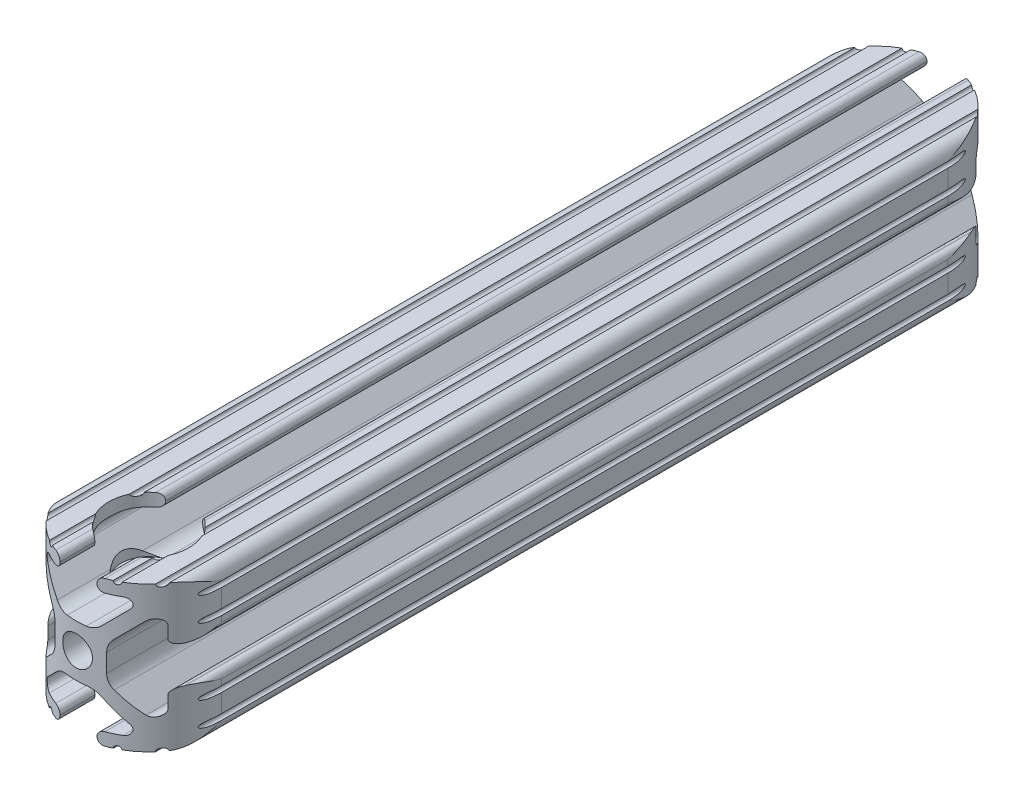
SolidWorks part; units mm, degrees
material "6061 Alloy"
ref_plane "Front Plane" through (0, 0, 0) normal (0, 0, 1) x (1, 0, 0)
ref_plane "Top Plane" through (0, 0, 0) normal (0, 1, 0) x (1, 0, 0)
ref_plane "Right Plane" through (0, 0, 0) normal (1, 0, 0) x (0, 0, -1)
sketch "Sketch1" plane through (0, 0, 0) normal (0, 0, 1) x (1, 0, 0)
  line L88 (-7.1797, -8.6452) -> (-3.9523, -5.4237)
  line L89 (-1.7093, -4.4958) -> (1.7093, -4.4958)
  line L90 (3.9523, -5.4237) -> (7.1797, -8.6452)
  line L91 (6.4164, -10.4902) -> (4.2875, -10.4902)
  line L92 (3.2385, -11.5392) -> (3.2385, -11.651)
  line L93 (4.2875, -12.7) -> (5.3171, -12.7)
  line L94 (6.3331, -12.7) -> (9.5504, -12.7)
  line L95 (12.7, -9.5504) -> (12.7, -6.3331)
  line L96 (12.7, -5.3171) -> (12.7, -4.2875)
  line L97 (11.651, -3.2385) -> (11.5392, -3.2385)
  line L98 (10.4902, -4.2875) -> (10.4902, -6.4021)
  line L99 (8.7371, -7.1294) -> (5.441, -3.8408)
  line L100 (4.5085, -1.5932) -> (4.5085, 1.5932)
  line L101 (5.441, 3.8408) -> (8.7371, 7.1294)
  line L102 (10.4902, 6.4021) -> (10.4902, 4.2875)
  line L103 (11.5392, 3.2385) -> (11.651, 3.2385)
  line L104 (12.7, 4.2875) -> (12.7, 5.3171)
  line L105 (12.7, 6.3331) -> (12.7, 9.5504)
  line L106 (9.5504, 12.7) -> (6.3331, 12.7)
  line L107 (5.3171, 12.7) -> (4.2875, 12.7)
  line L108 (3.2385, 11.651) -> (3.2385, 11.5392)
  line L109 (4.2875, 10.4902) -> (6.4768, 10.4902)
  line L110 (7.207, 8.7244) -> (3.8983, 5.4232)
  line L111 (1.6558, 4.4958) -> (-1.6558, 4.4958)
  line L112 (-3.8983, 5.4232) -> (-7.207, 8.7244)
  line L113 (-6.4768, 10.4902) -> (-4.2875, 10.4902)
  line L114 (-3.2385, 11.5392) -> (-3.2385, 11.651)
  line L115 (-4.2875, 12.7) -> (-5.3171, 12.7)
  line L116 (-6.3331, 12.7) -> (-9.5504, 12.7)
  line L117 (-12.7, 9.5504) -> (-12.7, 6.3331)
  line L118 (-12.7, 5.3171) -> (-12.7, 4.2875)
  line L119 (-11.651, 3.2385) -> (-11.5392, 3.2385)
  line L120 (-10.4902, 4.2875) -> (-10.4902, 6.4021)
  line L121 (-8.7371, 7.1294) -> (-5.441, 3.8408)
  line L122 (-4.5085, 1.5932) -> (-4.5085, -1.5932)
  line L123 (-5.441, -3.8408) -> (-8.7371, -7.1294)
  line L124 (-10.4902, -6.4021) -> (-10.4902, -4.2875)
  line L125 (-11.5392, -3.2385) -> (-11.651, -3.2385)
  line L126 (-12.7, -4.2875) -> (-12.7, -5.3171)
  line L127 (-12.7, -6.3331) -> (-12.7, -9.5504)
  line L128 (-9.5504, -12.7) -> (-6.3331, -12.7)
  line L129 (-5.3171, -12.7) -> (-4.2875, -12.7)
  line L130 (-3.2385, -11.651) -> (-3.2385, -11.5392)
  line L131 (-4.2875, -10.4902) -> (-6.4164, -10.4902)
  circle A1 centre (0, 0) radius 2.6035
  arc A104 (-7.1797, -8.6452) -> (-6.4164, -10.4902) centre (-6.4164, -9.4098) ccw
  arc A105 (-1.7093, -4.4958) -> (-3.9523, -5.4237) centre (-1.7093, -7.6708) ccw
  arc A106 (3.9523, -5.4237) -> (1.7093, -4.4958) centre (1.7093, -7.6708) ccw
  arc A107 (6.4164, -10.4902) -> (7.1797, -8.6452) centre (6.4164, -9.4098) ccw
  arc A108 (4.2875, -10.4902) -> (3.2385, -11.5392) centre (4.2875, -11.5392) ccw
  arc A109 (3.2385, -11.651) -> (4.2875, -12.7) centre (4.2875, -11.651) ccw
  arc A110 (6.3331, -12.7) -> (5.3171, -12.7) centre (5.8251, -12.7) ccw
  arc A111 (10.5664, -12.6998) -> (9.5504, -12.7) centre (10.0584, -12.7) ccw
  arc A112 (10.5664, -12.6998) -> (12.6998, -10.5664) centre (10.5918, -10.5918) ccw
  arc A113 (12.7, -9.5504) -> (12.6998, -10.5664) centre (12.7, -10.0584) ccw
  arc A114 (12.7, -5.3171) -> (12.7, -6.3331) centre (12.7, -5.8251) ccw
  arc A115 (12.7, -4.2875) -> (11.651, -3.2385) centre (11.651, -4.2875) ccw
  arc A116 (11.5392, -3.2385) -> (10.4902, -4.2875) centre (11.5392, -4.2875) ccw
  arc A117 (8.7371, -7.1294) -> (10.4902, -6.4021) centre (9.4628, -6.4021) ccw
  arc A118 (4.5085, -1.5932) -> (5.441, -3.8408) centre (7.6835, -1.5932) ccw
  arc A119 (5.441, 3.8408) -> (4.5085, 1.5932) centre (7.6835, 1.5932) ccw
  arc A120 (10.4902, 6.4021) -> (8.7371, 7.1294) centre (9.4628, 6.4021) ccw
  arc A121 (10.4902, 4.2875) -> (11.5392, 3.2385) centre (11.5392, 4.2875) ccw
  arc A122 (11.651, 3.2385) -> (12.7, 4.2875) centre (11.651, 4.2875) ccw
  arc A123 (12.7, 6.3331) -> (12.7, 5.3171) centre (12.7, 5.8251) ccw
  arc A124 (12.6998, 10.5664) -> (12.7, 9.5504) centre (12.7, 10.0584) ccw
  arc A125 (12.6998, 10.5664) -> (10.5664, 12.6998) centre (10.5918, 10.5918) ccw
  arc A126 (9.5504, 12.7) -> (10.5664, 12.6998) centre (10.0584, 12.7) ccw
  arc A127 (5.3171, 12.7) -> (6.3331, 12.7) centre (5.8251, 12.7) ccw
  arc A128 (4.2875, 12.7) -> (3.2385, 11.651) centre (4.2875, 11.651) ccw
  arc A129 (3.2385, 11.5392) -> (4.2875, 10.4902) centre (4.2875, 11.5392) ccw
  arc A130 (7.207, 8.7244) -> (6.4768, 10.4902) centre (6.4768, 9.4563) ccw
  arc A131 (1.6558, 4.4958) -> (3.8983, 5.4232) centre (1.6558, 7.6708) ccw
  arc A132 (-3.8983, 5.4232) -> (-1.6558, 4.4958) centre (-1.6558, 7.6708) ccw
  arc A133 (-6.4768, 10.4902) -> (-7.207, 8.7244) centre (-6.4768, 9.4563) ccw
  arc A134 (-4.2875, 10.4902) -> (-3.2385, 11.5392) centre (-4.2875, 11.5392) ccw
  arc A135 (-3.2385, 11.651) -> (-4.2875, 12.7) centre (-4.2875, 11.651) ccw
  arc A136 (-6.3331, 12.7) -> (-5.3171, 12.7) centre (-5.8251, 12.7) ccw
  arc A137 (-10.5664, 12.6998) -> (-9.5504, 12.7) centre (-10.0584, 12.7) ccw
  arc A138 (-10.5664, 12.6998) -> (-12.6998, 10.5664) centre (-10.5918, 10.5918) ccw
  arc A139 (-12.7, 9.5504) -> (-12.6998, 10.5664) centre (-12.7, 10.0584) ccw
  arc A140 (-12.7, 5.3171) -> (-12.7, 6.3331) centre (-12.7, 5.8251) ccw
  arc A141 (-12.7, 4.2875) -> (-11.651, 3.2385) centre (-11.651, 4.2875) ccw
  arc A142 (-11.5392, 3.2385) -> (-10.4902, 4.2875) centre (-11.5392, 4.2875) ccw
  arc A143 (-8.7371, 7.1294) -> (-10.4902, 6.4021) centre (-9.4628, 6.4021) ccw
  arc A144 (-4.5085, 1.5932) -> (-5.441, 3.8408) centre (-7.6835, 1.5932) ccw
  arc A145 (-5.441, -3.8408) -> (-4.5085, -1.5932) centre (-7.6835, -1.5932) ccw
  arc A146 (-10.4902, -6.4021) -> (-8.7371, -7.1294) centre (-9.4628, -6.4021) ccw
  arc A147 (-10.4902, -4.2875) -> (-11.5392, -3.2385) centre (-11.5392, -4.2875) ccw
  arc A148 (-11.651, -3.2385) -> (-12.7, -4.2875) centre (-11.651, -4.2875) ccw
  arc A149 (-12.7, -6.3331) -> (-12.7, -5.3171) centre (-12.7, -5.8251) ccw
  arc A150 (-12.6998, -10.5664) -> (-12.7, -9.5504) centre (-12.7, -10.0584) ccw
  arc A151 (-12.6998, -10.5664) -> (-10.5664, -12.6998) centre (-10.5918, -10.5918) ccw
  arc A152 (-9.5504, -12.7) -> (-10.5664, -12.6998) centre (-10.0584, -12.7) ccw
  arc A153 (-5.3171, -12.7) -> (-6.3331, -12.7) centre (-5.8251, -12.7) ccw
  arc A154 (-4.2875, -12.7) -> (-3.2385, -11.651) centre (-4.2875, -11.651) ccw
  arc A155 (-3.2385, -11.5392) -> (-4.2875, -10.4902) centre (-4.2875, -11.5392) ccw
extrude "Boss-Extrude1" add sketch "Sketch1" along normal mid plane 152.4
sketch "Sketch2" plane through (0, 12.7, 0) normal (0, 1, 0) x (1, 0, 0)
  line L0 (0, 76.2) -> (0, -76.2) construction
  line L1 (-12.7, 76.2) -> (12.7, 76.2)
  line L2 (-12.7, 76.2) -> (-12.7, -76.2)
  line L3 (-12.7, -76.2) -> (12.7, -76.2)
  line L4 (12.7, 76.2) -> (12.7, -76.2)
  circle A0 centre (0, 63.5) radius 12.7
  circle A1 centre (0, -63.5) radius 12.7
  circle A2 centre (0, -63.5) radius 3.175
  line M5 (-6.3331, 76.2) -> (-9.5504, 76.2)
  line M6 (-9.5504, 76.2) -> (-9.5504, -76.2)
  line M7 (-9.5504, -76.2) -> (-6.3331, -76.2)
  line M8 (-6.3331, -76.2) -> (-6.3331, 76.2)
  dimension "D1" = 6.35
extrude "Cut-Extrude1" cut sketch "Sketch2" against normal through all both and the other way through all contours A2 L0 | L0 A2 | A1 L2 L3 M6 | A1 M6 M7 M8 | A1 L3 M8 | A1 L3 L4 | A0 L4 L1 | A0 M8 M5 M6 | A0 L1 M8 | A0 L1 L2 M6 region at (-4.7717, 12.7, -75.6988) region at (9.8632, 12.7, -73.3632) region at (-8.1865, 12.7, -74.6688) region at (-11.3727, 12.7, -72.4456) region at (9.8632, 12.7, 73.3632) region at (1.3475, 12.7, 63.5) region at (-1.3475, 12.7, 63.5) region at (-4.7717, 12.7, 75.6988) region at (-8.1865, 12.7, 74.6688) region at (-11.3727, 12.7, 72.4456)
sketch "Sketch3" plane through (0, 12.7, 0) normal (0, 1, 0) x (1, 0, 0)
  circle A0 centre (0, -63.5) radius 6.35 construction
  circle A1 centre (0, -63.5) radius 4.8006
  circle A2 centre (0, -63.5) radius 6.985
  line M5 (6.3331, 74.5082) -> (6.3331, -74.5082)
  dimension "D1" = 12.7
  dimension "D2" = 9.6012
  dimension "D3" = 0.635
extrude "Cut-Extrude2" cut sketch "Sketch3" against normal up to vertex (8.2042 mm away) contours A1 | A0 A1 M5 | A2 M5 region at (0, 12.7, 63.5) region at (6.5949, 12.7, 63.5) region at (6.1401, 12.7, 63.5) up to point (-7.207, 8.7244, 73.957)
extrude "Cut-Extrude4" cut sketch "Sketch3<3>" along normal blind 3.9756 from surface contours A1 | A0 A1 M5 | A2 M5 region at (0, 12.7, 63.5) region at (6.5949, 12.7, 63.5) region at (6.1401, 12.7, 63.5) starting at face at (7.9961, -12.7, 0)
sketch "Sketch3<3>" plane through (0, 12.7, 0) normal (0, 1, 0) x (1, 0, 0) same geometry as "Sketch3"
extrude "Cut-Extrude5" cut sketch "Sketch3<5>" against normal up to surface (8.2042 mm away) contours A1 region at (0, 12.7, 63.5) up to face at (0, 4.4958, 71.2939)
sketch "Sketch3<5>" plane through (0, 12.7, 0) normal (0, 1, 0) x (1, 0, 0) same geometry as "Sketch3"
extrude "Cut-Extrude6" cut sketch "Sketch3<6>" along normal up to surface (8.2042 mm away) from surface contours A1 region at (0, 12.7, 63.5) up to face at (0, -4.4958, 71.2838) starting at face at (7.5504, -12.7, 21.1667)
sketch "Sketch3<6>" plane through (0, 12.7, 0) normal (0, 1, 0) x (1, 0, 0) same geometry as "Sketch3"
